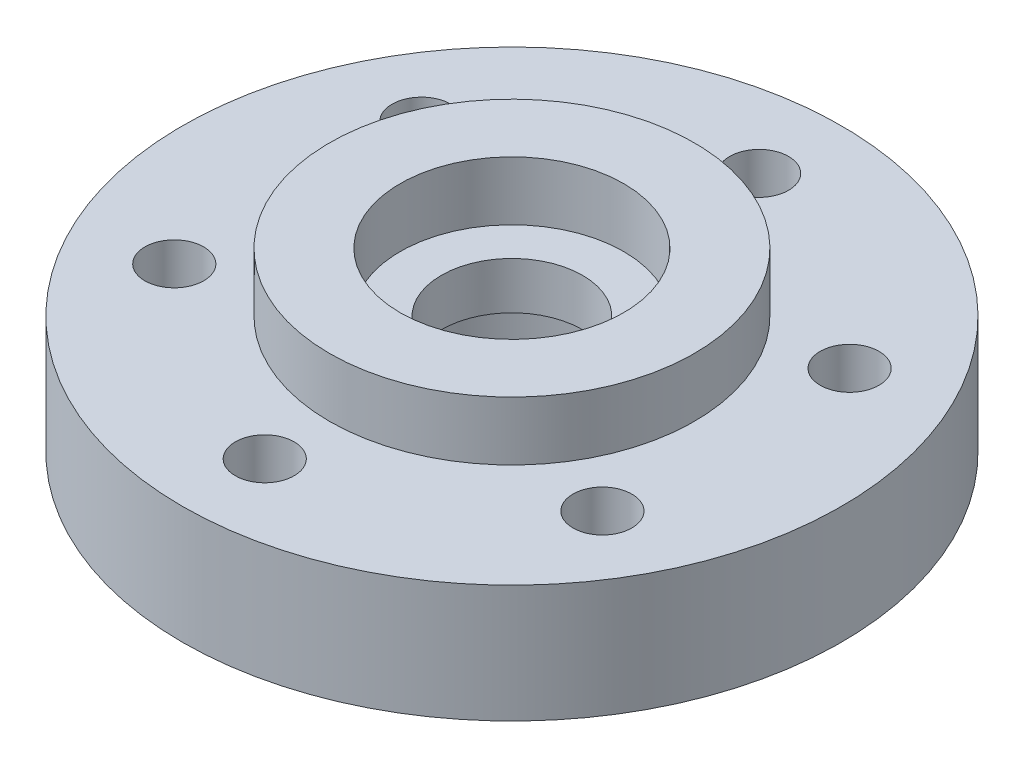
SolidWorks part; units mm, degrees
ref_plane "Front Plane" through (0, 0, 0) normal (0, 0, 1) x (1, 0, 0)
ref_plane "Top Plane" through (0, 0, 0) normal (0, 1, 0) x (1, 0, 0)
ref_plane "Right Plane" through (0, 0, 0) normal (1, 0, 0) x (0, 0, -1)
sketch "Sketch1" plane through (0, 0, 0) normal (0, 1, 0) x (1, 0, 0)
  circle A0 centre (0, 0) radius 21 construction
  circle A1 centre (0, 21) radius 2.5
  circle A2 centre (18.1865, 10.5) radius 2.5
  circle A3 centre (18.1865, -10.5) radius 2.5
  circle A4 centre (0, -21) radius 2.5
  circle A5 centre (-18.1865, -10.5) radius 2.5
  circle A6 centre (-18.1865, 10.5) radius 2.5
  circle A7 centre (0, 0) radius 28
  circle A8 centre (0, 0) radius 6
  point P18 (0, 0)
  dimension "D1" = 42
  dimension "D2" = 5
  dimension "D4" = 56
  dimension "D5" = 12
  dimension "D3" = 6
extrude "Boss-Extrude1" add sketch "Sketch1" along normal blind 10
sketch "Sketch2" plane through (0, 10, 0) normal (0, 1, 0) x (1, 0, 0)
  circle A0 centre (0, 0) radius 9.5
  circle A1 centre (0, 0) radius 15.5
  dimension "D1" = 19
  dimension "D2" = 6
extrude "Boss-Extrude2" add sketch "Sketch2" along normal blind 5
sketch "Sketch3" plane through (0, 0, 0) normal (0, -1, 0) x (1, 0, 0)
  circle A0 centre (0, 0) radius 11
  dimension "D1" = 22
extrude "Cut-Extrude1" cut sketch "Sketch3" against normal blind 6
